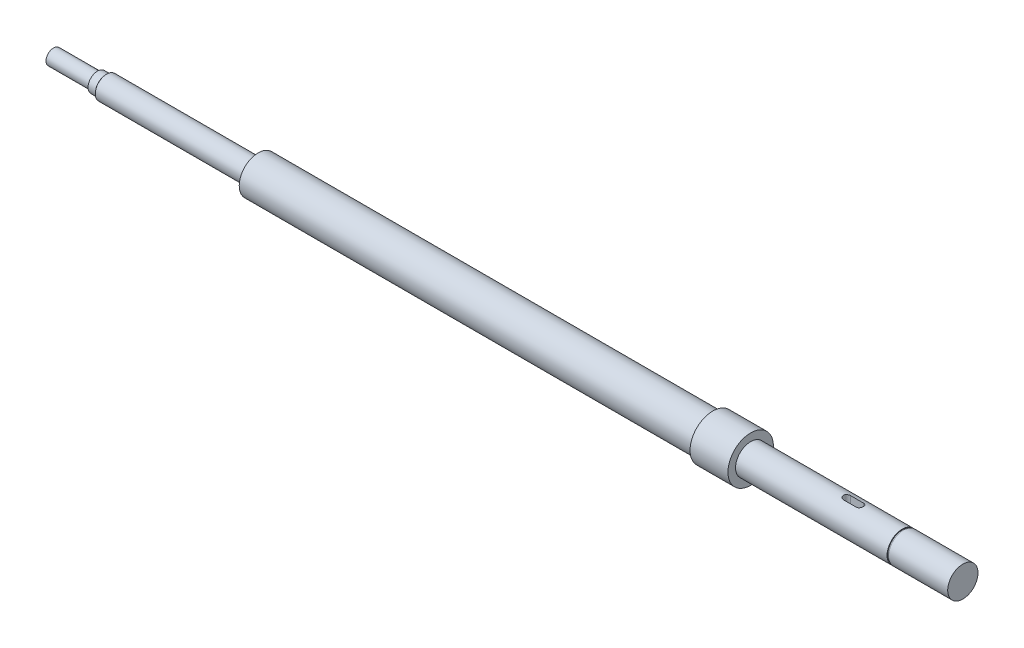
SolidWorks part; units mm, degrees
ref_plane "Front Plane" through (0, 0, 0) normal (0, 0, 1) x (1, 0, 0)
ref_plane "Top Plane" through (0, 0, 0) normal (0, 1, 0) x (1, 0, 0)
ref_plane "Right Plane" through (0, 0, 0) normal (1, 0, 0) x (0, 0, -1)
sketch "Sketch1" plane through (0, 0, 0) normal (1, 0, 0) x (0, 0, -1)
  circle A0 centre (0, 0) radius 500
extrude "Boss-Extrude1" add sketch "Sketch1" along normal blind 600
sketch "Sketch2" plane through (0, 0, 0) normal (-1, 0, 0) x (0, 0, 1)
  circle A0 centre (0, 0) radius 5
extrude "Cut-Extrude1" cut sketch "Sketch2" against normal blind 29 flip side to cut
sketch "Sketch3" plane through (29, 0, 0) normal (-1, 0, 0) x (0, 0, 1)
  circle A0 centre (0, 0) radius 6.25
extrude "Cut-Extrude2" cut sketch "Sketch3" against normal blind 5 flip side to cut
sketch "Sketch4" plane through (34, 0, 0) normal (-1, 0, 0) x (0, 0, 1)
  circle A0 centre (0, 0) radius 5.75
extrude "Cut-Extrude3" cut sketch "Sketch4" against normal blind 1 flip side to cut
sketch "Sketch5" plane through (35, 0, 0) normal (-1, 0, 0) x (0, 0, 1)
  circle A0 centre (0, 0) radius 7.5
extrude "Cut-Extrude4" cut sketch "Sketch5" against normal blind 100 flip side to cut
sketch "Sketch6" plane through (135, 0, 0) normal (-1, 0, 0) x (0, 0, 1)
  circle A0 centre (0, 0) radius 12.5
extrude "Cut-Extrude5" cut sketch "Sketch6" against normal blind 300 flip side to cut
sketch "Sketch7" plane through (435, 0, 0) normal (-1, 0, 0) x (0, 0, 1)
  circle A0 centre (0, 0) radius 15
extrude "Cut-Extrude6" cut sketch "Sketch7" against normal blind 25 flip side to cut
sketch "Sketch8" plane through (460, 0, 0) normal (-1, 0, 0) x (0, 0, 1)
  circle A0 centre (0, 0) radius 10
extrude "Cut-Extrude7" cut sketch "Sketch8" against normal blind 100 flip side to cut
sketch "Sketch9" plane through (560, 0, 0) normal (-1, 0, 0) x (0, 0, 1)
  circle A0 centre (0, 0) radius 9.5
extrude "Cut-Extrude8" cut sketch "Sketch9" against normal blind 1 flip side to cut
sketch "Sketch10" plane through (561, 0, 0) normal (-1, 0, 0) x (0, 0, 1)
  circle A0 centre (0, 0) radius 10
extrude "Cut-Extrude10" cut sketch "Sketch10" against normal up to surface (39 mm away) flip side to cut up to face at (600, 0, -500)
ref_plane "Plane1" through (0, 30, 0) normal (0, 1, 0) x (1, 0, 0)
sketch "Sketch14" plane through (0, 30, 0) normal (0, 1, 0) x (1, 0, 0)
  line L0 (18.8903, 0) -> (24.9423, 0) construction
  line L1 (18.8903, 1.4059) -> (24.9423, 1.4059)
  line L2 (18.8903, -1.4059) -> (24.9423, -1.4059)
  line L3 (523.6203, 0) -> (532.0104, 0) construction
  line L4 (523.6203, 2.3655) -> (532.0104, 2.3655)
  line L5 (523.6203, -2.3655) -> (532.0104, -2.3655)
  arc A0 (18.8903, 1.4059) -> (18.8903, -1.4059) centre (18.8903, 0) ccw
  arc A1 (24.9423, -1.4059) -> (24.9423, 1.4059) centre (24.9423, 0) ccw
  arc A2 (523.6203, 2.3655) -> (523.6203, -2.3655) centre (523.6203, 0) ccw
  arc A3 (532.0104, -2.3655) -> (532.0104, 2.3655) centre (532.0104, 0) ccw
  point P2 (21.9163, 0)
  point P10 (527.8153, 0)
  point P15 (0, 0)
  point P16 (522.0845, 0)
  point P17 (523.6203, -1.4059)
split line "Split Line1"
extrude "Cut-Extrude11" cut sketch "Sketch14<3>" against normal blind 25
sketch "Sketch14<3>" plane through (0, 30, 0) normal (0, 1, 0) x (1, 0, 0) same geometry as "Sketch14"
